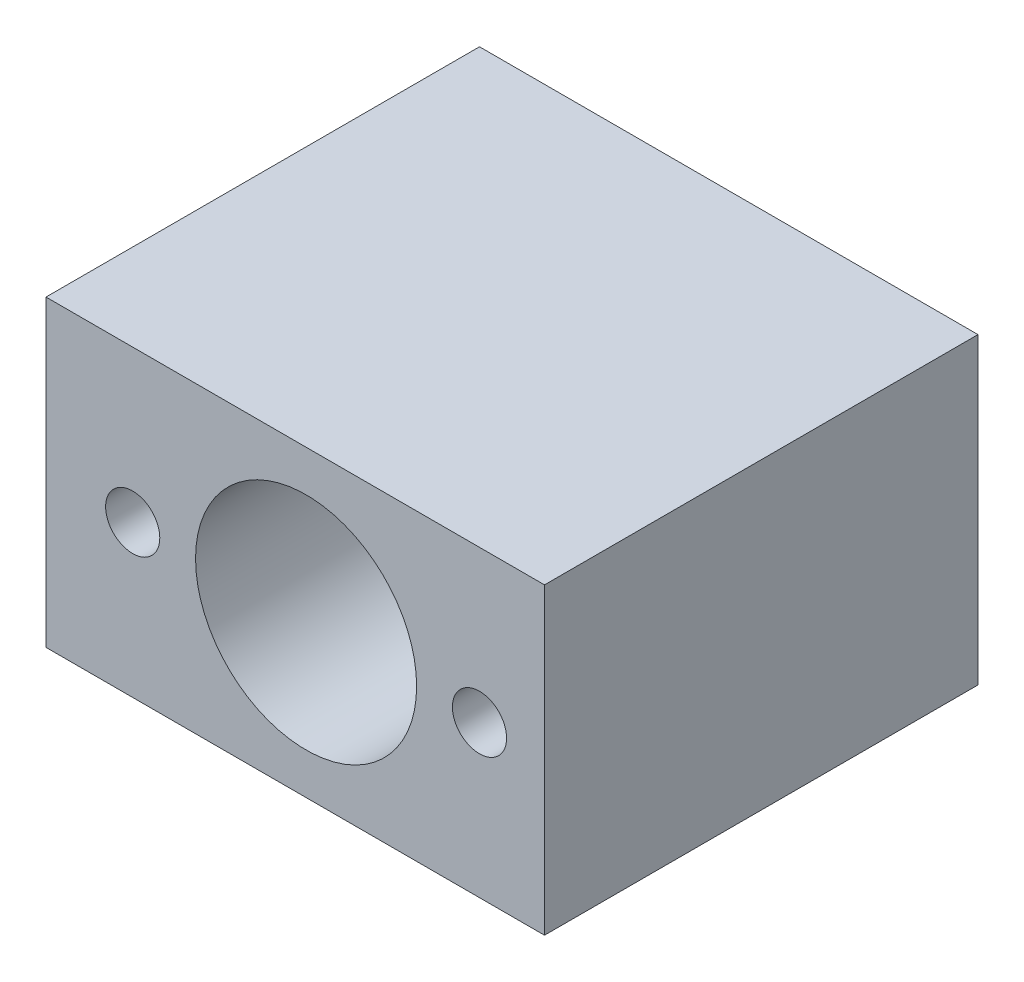
SolidWorks part; units mm, degrees
ref_plane "Alzado" through (0, 0, 0) normal (0, 0, 1) x (1, 0, 0)
ref_plane "Planta" through (0, 0, 0) normal (0, 1, 0) x (1, 0, 0)
ref_plane "Vista lateral" through (0, 0, 0) normal (1, 0, 0) x (0, 0, -1)
sketch "Croquis1" plane through (0, 0, 0) normal (0, 0, 1) x (1, 0, 0)
  line L1 (0, 0) -> (23, 0)
  line L2 (0, 0) -> (0, 14)
  line L3 (0, 14) -> (23, 14)
  line L4 (23, 0) -> (23, 14)
  circle A0 centre (12, 7) radius 5.1
  dimension "D9" = 10.2
  dimension "D1" = 14
  dimension "D2" = 23
  dimension "D3" = 12
  dimension "D4" = 7
extrude "Saliente-Extruir1" add sketch "Croquis1" along normal blind 20
hole_wizard "Perforador para roscar para macho de roscar para M31" positions "Croquis2" profile "Croquis3" hole size "M3" standard "DIN"
sketch "Croquis2" plane through (0, 0, 20) normal (0, 0, 1) x (1, 0, 0)
  line L0 (0, 0) -> (23, 0) construction
  circle A0 centre (12, 7) radius 5.1 construction
  point P0 (4, 7)
  point P2 (20, 7)
  point P7 (20, 7)
  point P8 (4, 7)
  dimension "D1" = 8
  dimension "D2" = 8
  dimension "D3" = 7
  dimension "D4" = 7
sketch "Croquis3" plane through (4, 7, 20) normal (1, 0, 0) x (0, -1, 0)
  line L0 (0, 0) -> (0, 12.7511)
  line L1 (0, 12.7511) -> (1.25, 12)
  line L2 (1.25, 12) -> (1.25, 0)
  line L5 (1.25, 0) -> (0, 0)
  line L10 (0, 12.7511) -> (-1.25, 12) construction
  line L11 (0, -6.35) -> (0, 107.95) construction
  dimension "Diámetro de taladro" = 2.5
  dimension "Profundidad de taladro" = 12
  dimension "Ángulo de perforador" = 118
